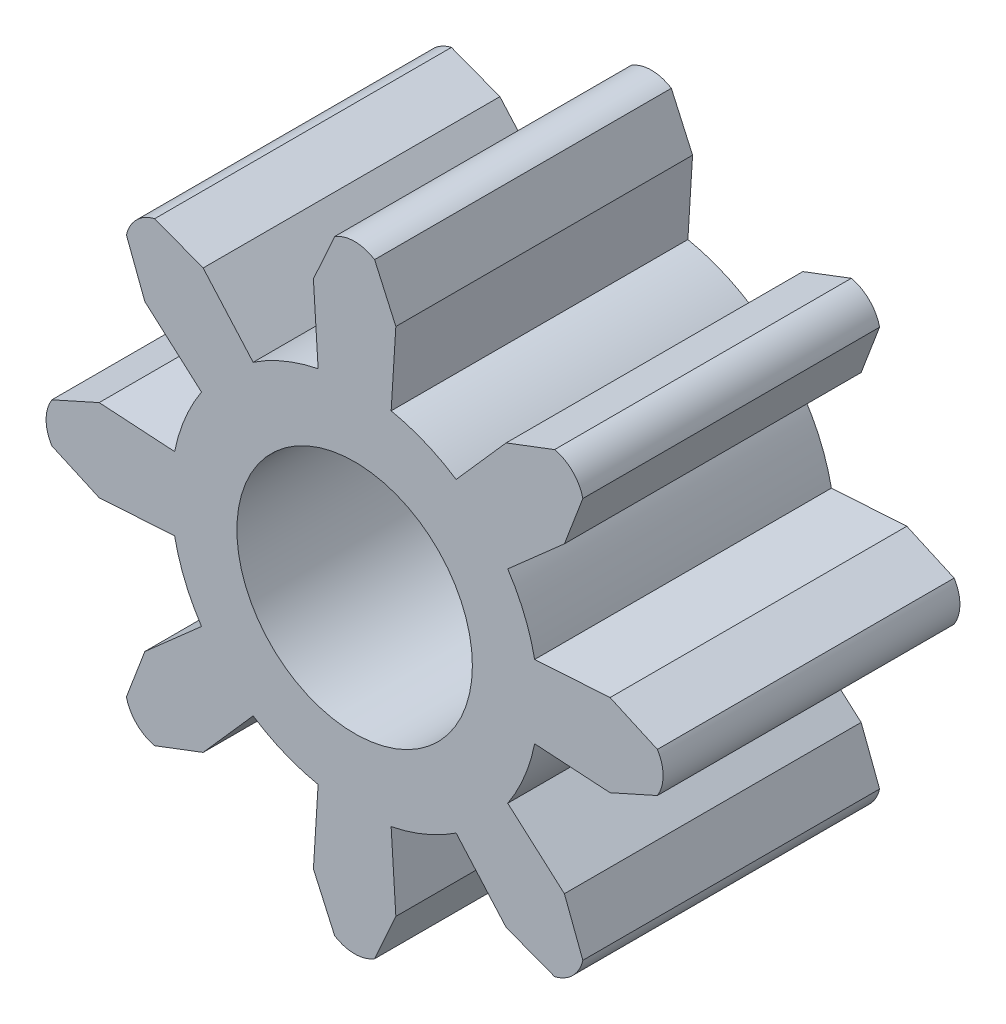
SolidWorks part; units mm, degrees
ref_plane "Przednia" through (0, 0, 0) normal (0, 0, 1) x (1, 0, 0)
ref_plane "Górna" through (0, 0, 0) normal (0, 1, 0) x (1, 0, 0)
ref_plane "Prawa" through (0, 0, 0) normal (1, 0, 0) x (0, 0, -1)
sketch "Szkic1" plane through (0, 0, 0) normal (0, 0, 1) x (1, 0, 0)
  line L0 (0, 0) -> (0, 7.2138) construction
  line L1 (0.875, 5.4234) -> (0.775, 3.8222)
  line L2 (0.875, 5.4234) -> (0.4241, 6.4277)
  line L3 (-0.875, 5.4234) -> (-0.4241, 6.4277)
  line L4 (-0.875, 5.4234) -> (-0.775, 3.8222)
  line L5 (4.4536, 3.2162) -> (3.2507, 2.1547)
  line L6 (4.4536, 3.2162) -> (4.845, 4.2452)
  line L7 (3.2162, 4.4536) -> (4.2452, 4.845)
  line L8 (3.2162, 4.4536) -> (2.1547, 3.2507)
  line L9 (0, 0) -> (5.1009, 5.1009) construction
  line L10 (5.4234, -0.875) -> (3.8222, -0.775)
  line L11 (5.4234, -0.875) -> (6.4277, -0.4241)
  line L12 (5.4234, 0.875) -> (6.4277, 0.4241)
  line L13 (5.4234, 0.875) -> (3.8222, 0.775)
  line L14 (0, 0) -> (7.2138, 0) construction
  line L15 (3.2162, -4.4536) -> (2.1547, -3.2507)
  line L16 (3.2162, -4.4536) -> (4.2452, -4.845)
  line L17 (4.4536, -3.2162) -> (4.845, -4.2452)
  line L18 (4.4536, -3.2162) -> (3.2507, -2.1547)
  line L19 (0, 0) -> (5.1009, -5.1009) construction
  line L20 (-0.875, -5.4234) -> (-0.775, -3.8222)
  line L21 (-0.875, -5.4234) -> (-0.4241, -6.4277)
  line L22 (0.875, -5.4234) -> (0.4241, -6.4277)
  line L23 (0.875, -5.4234) -> (0.775, -3.8222)
  line L24 (0, 0) -> (0, -7.2138) construction
  line L25 (-4.4536, -3.2162) -> (-3.2507, -2.1547)
  line L26 (-4.4536, -3.2162) -> (-4.845, -4.2452)
  line L27 (-3.2162, -4.4536) -> (-4.2452, -4.845)
  line L28 (-3.2162, -4.4536) -> (-2.1547, -3.2507)
  line L29 (0, 0) -> (-5.1009, -5.1009) construction
  line L30 (-5.4234, 0.875) -> (-3.8222, 0.775)
  line L31 (-5.4234, 0.875) -> (-6.4277, 0.4241)
  line L32 (-5.4234, -0.875) -> (-6.4277, -0.4241)
  line L33 (-5.4234, -0.875) -> (-3.8222, -0.775)
  line L34 (0, 0) -> (-7.2138, 0) construction
  line L35 (-3.2162, 4.4536) -> (-2.1547, 3.2507)
  line L36 (-3.2162, 4.4536) -> (-4.2452, 4.845)
  line L37 (-4.4536, 3.2162) -> (-4.845, 4.2452)
  line L38 (-4.4536, 3.2162) -> (-3.2507, 2.1547)
  line L39 (0, 0) -> (-5.1009, 5.1009) construction
  circle A0 centre (0, 0) radius 2.5
  circle A1 centre (0, 0) radius 6.55 construction
  arc A2 (-0.775, 3.8222) -> (0.775, 3.8222) centre (0, 0) ccw construction
  arc A3 (0.4241, 6.4277) -> (0, 6.55) centre (0, 5.7533) ccw
  arc A4 (-0.4241, 6.4277) -> (0, 6.55) centre (0, 5.7533) cw
  circle A5 centre (0, 0) radius 2.5
  arc A6 (4.845, 4.2452) -> (4.6315, 4.6315) centre (4.0682, 4.0682) ccw
  arc A7 (4.2452, 4.845) -> (4.6315, 4.6315) centre (4.0682, 4.0682) cw
  circle A8 centre (0, 0) radius 6.55 construction
  circle A9 centre (0, 0) radius 3.9 construction
  circle A10 centre (0, 0) radius 2.5
  arc A11 (6.4277, -0.4241) -> (6.55, 0) centre (5.7533, 0) ccw
  arc A12 (6.4277, 0.4241) -> (6.55, 0) centre (5.7533, 0) cw
  circle A13 centre (0, 0) radius 6.55 construction
  circle A14 centre (0, 0) radius 3.9 construction
  circle A15 centre (0, 0) radius 2.5
  arc A16 (4.2452, -4.845) -> (4.6315, -4.6315) centre (4.0682, -4.0682) ccw
  arc A17 (4.845, -4.2452) -> (4.6315, -4.6315) centre (4.0682, -4.0682) cw
  circle A18 centre (0, 0) radius 6.55 construction
  circle A19 centre (0, 0) radius 3.9 construction
  circle A20 centre (0, 0) radius 2.5
  arc A21 (-0.4241, -6.4277) -> (0, -6.55) centre (0, -5.7533) ccw
  arc A22 (0.4241, -6.4277) -> (0, -6.55) centre (0, -5.7533) cw
  circle A23 centre (0, 0) radius 6.55 construction
  circle A24 centre (0, 0) radius 3.9 construction
  circle A25 centre (0, 0) radius 2.5
  arc A26 (-4.845, -4.2452) -> (-4.6315, -4.6315) centre (-4.0682, -4.0682) ccw
  arc A27 (-4.2452, -4.845) -> (-4.6315, -4.6315) centre (-4.0682, -4.0682) cw
  circle A28 centre (0, 0) radius 6.55 construction
  circle A29 centre (0, 0) radius 3.9 construction
  circle A30 centre (0, 0) radius 2.5
  arc A31 (-6.4277, 0.4241) -> (-6.55, 0) centre (-5.7533, 0) ccw
  arc A32 (-6.4277, -0.4241) -> (-6.55, 0) centre (-5.7533, 0) cw
  circle A33 centre (0, 0) radius 6.55 construction
  circle A34 centre (0, 0) radius 3.9 construction
  circle A35 centre (0, 0) radius 2.5
  arc A36 (-4.2452, 4.845) -> (-4.6315, 4.6315) centre (-4.0682, 4.0682) ccw
  arc A37 (-4.845, 4.2452) -> (-4.6315, 4.6315) centre (-4.0682, 4.0682) cw
  circle A38 centre (0, 0) radius 6.55 construction
  circle A39 centre (0, 0) radius 3.9 construction
  arc A40 (-0.775, 3.8222) -> (-2.1547, 3.2507) centre (0, 0) ccw
  arc A41 (-3.2507, 2.1547) -> (-3.8222, 0.775) centre (0, 0) ccw
  arc A42 (-3.8222, -0.775) -> (-3.2507, -2.1547) centre (0, 0) ccw
  arc A43 (-2.1547, -3.2507) -> (-0.775, -3.8222) centre (0, 0) ccw
  arc A44 (0.775, -3.8222) -> (2.1547, -3.2507) centre (0, 0) ccw
  arc A45 (3.2507, -2.1547) -> (3.8222, -0.775) centre (0, 0) ccw
  arc A46 (3.8222, 0.775) -> (3.2507, 2.1547) centre (0, 0) ccw
  arc A47 (2.1547, 3.2507) -> (0.775, 3.8222) centre (0, 0) ccw
  point P108 (0, 0)
  dimension "D1" = 5
  dimension "D2" = 13.1
  dimension "D3" = 7.8
  dimension "D4" = 1.75
  dimension "D5" = 1.55
extrude "Dodanie-wyciągnięcie1" add sketch "Szkic1" along normal blind 6.3 contours L8 A47 L1 L2 A3 A4 L3 L4 A40 L35 L36 A36 A37 L37 L38 A41 L30 L31 A31 A32 L32 L33 A42 L25 L26 A26 A27 L27 L28 A43 L20 L21 A21 A22 L22 L23 A44 L15 L16 A16 A17 L17 L18 A45 L10 L11 A11 A12 L12 L13 A46 region at (0.6401, 4.6344, 0)
